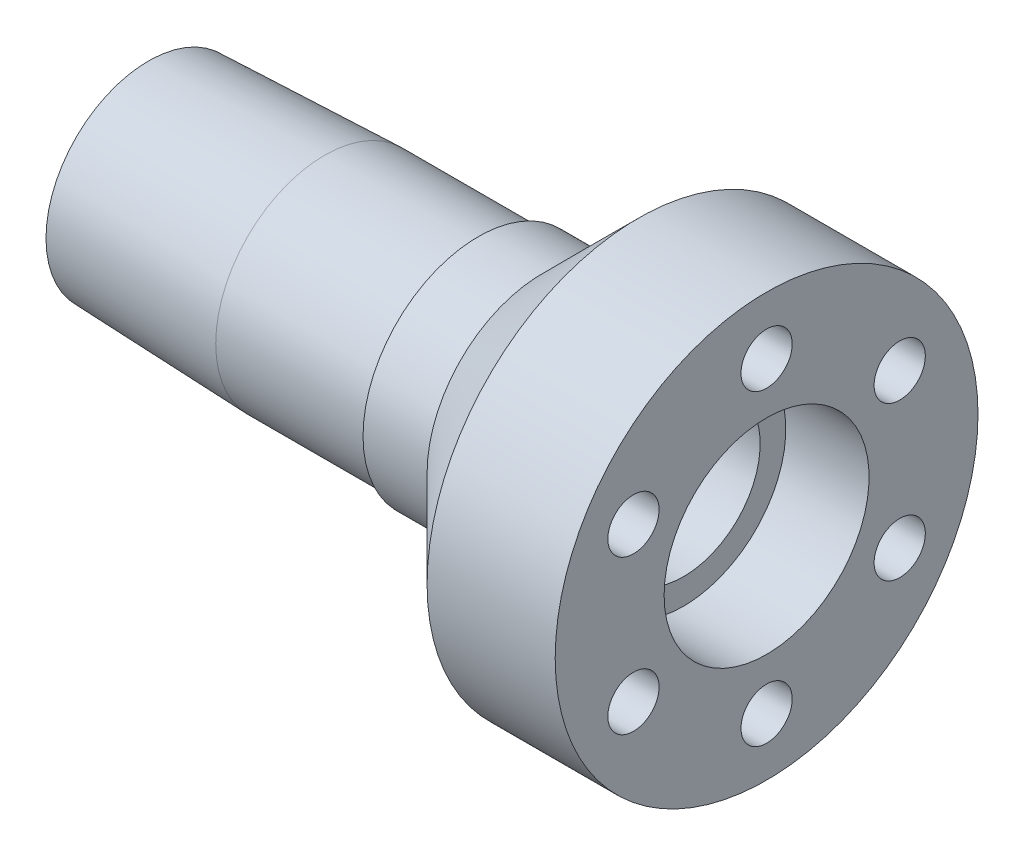
SolidWorks part; units mm, degrees
ref_plane "Front Plane" through (0, 0, 0) normal (0, 0, 1) x (1, 0, 0)
ref_plane "Top Plane" through (0, 0, 0) normal (0, 1, 0) x (1, 0, 0)
ref_plane "Right Plane" through (0, 0, 0) normal (1, 0, 0) x (0, 0, -1)
sketch "Sketch2" plane through (0, 0, 0) normal (0, 0, 1) x (1, 0, 0)
  line L0 (0, 0) -> (64.6823, 0) construction
  line L1 (0, 8) -> (0, 6)
  line L2 (0, 6) -> (41.75, 6)
  line L7 (48.25, 8) -> (48.25, 16.5024)
  line L8 (48.25, 16.5024) -> (38.25, 16.5024)
  line L11 (41.75, 6) -> (41.75, 8)
  line L12 (41.75, 8) -> (48.25, 8)
  line L15 (30.7476, 9) -> (38.25, 16.5024)
  line L16 (0, 8) -> (13.7476, 8.5)
  line L17 (13.7476, 8.5) -> (25.7476, 8.5)
  line L19 (25.7476, 8.5) -> (25.7476, 9)
  line L20 (25.7476, 9) -> (30.7476, 9)
  dimension "D1" = 8.5
  dimension "D2" = 6
  dimension "D3" = 8
  dimension "D4" = 6.5
  dimension "D5" = 0.5
  dimension "D6" = 45
  dimension "D7" = 10
  dimension "D8" = 41.75
  dimension "D9" = 12
  dimension "D10" = 8.5024
  dimension "D11" = 8
  dimension "D12" = 5
revolve "Revolve1" add sketch "Sketch2" angle 360 about L0
sketch "Sketch7" plane through (48.25, 0, 0) normal (1, 0, 0) x (0, 0, -1)
  line L0 (0, -16.5024) -> (0, 16.5024) construction
  circle A0 centre (0, 12) radius 2
  circle A1 centre (0, 0) radius 16.5024 construction
  circle A3 centre (10.3923, 6) radius 2
  circle A4 centre (10.3923, -6) radius 2
  circle A5 centre (0, -12) radius 2
  circle A6 centre (-10.3923, -6) radius 2
  circle A7 centre (-10.3923, 6) radius 2
  point P20 (0, 0)
  dimension "D1" = 4
  dimension "D2" = 12
  dimension "D3" = 6
extrude "Cut-Extrude2" cut sketch "Sketch7" against normal blind 8
